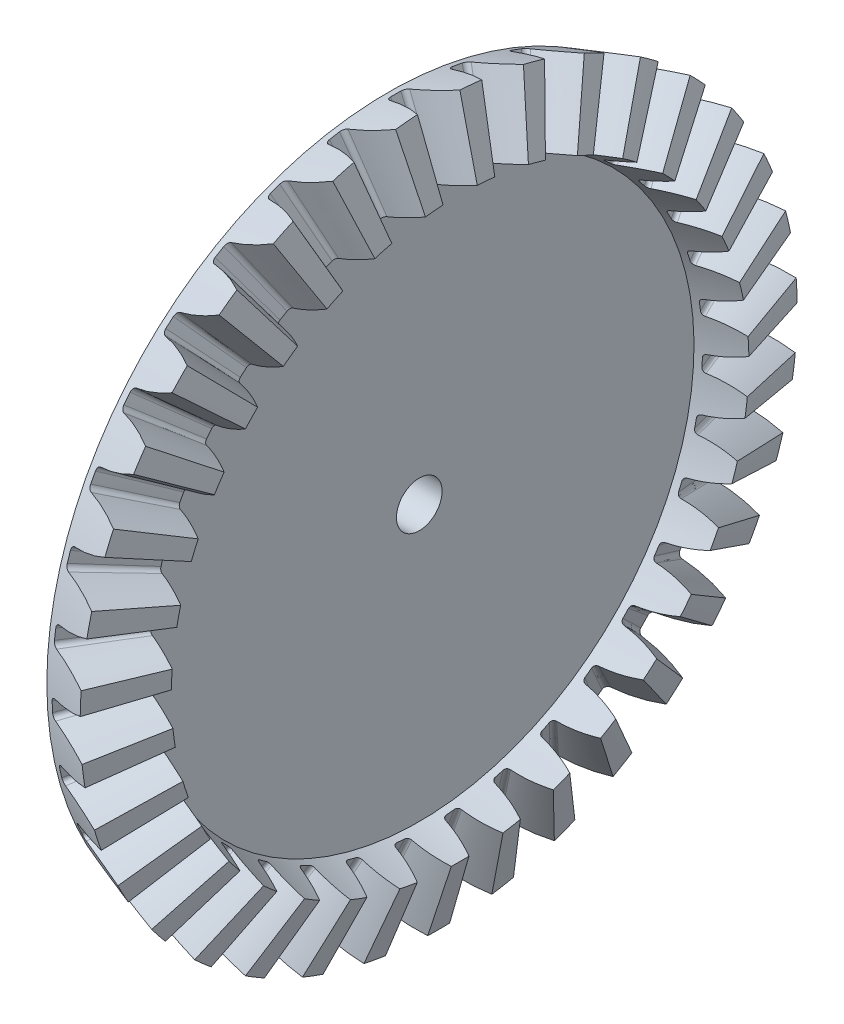
SolidWorks part; units mm, degrees
revolve "Base-Revolve" add sketch "BasProSke" angle 360 about L0 other way angle 5.143
sketch "BasProSke" plane through (0, 0, 0) normal (0, 1, 0) x (1, 0, 0)
  line L0 (-10, 0) -> (60, 0) construction
  line L1 (0, 0) -> (0, 17.8164)
  line L2 (0, 0) -> (1.6355, 0)
  line L3 (1.6355, 0) -> (1.6355, 14.3494)
  line L4 (8.4047, 0) -> (-8.2294, 48.5163) construction
  line L5 (0, 17.8164) -> (2.6495, 18.7247)
  line L6 (8.4047, 0) -> (-21.3703, 96.8732) construction
  line L7 (8.4047, 0) -> (0, 17.8164) construction
  line L8 (2.6495, 18.7247) -> (3.7694, 15.081)
  line L9 (3.7694, 15.081) -> (1.6355, 14.3494)
  line L10 (2.0547, 18.5208) -> (-9.9296, 18.5208) construction
  dimension "D1" = 35.6327
  dimension "D2" = 8.4047
  dimension "D3" = 19.5792
  dimension "D4" = 1.839
material "Plain Carbon Steel"
ref_plane "Plane1" through (0, 0, 0) normal (0, 0, 1) x (1, 0, 0)
ref_plane "Plane2" through (0, 0, 0) normal (0, 1, 0) x (1, 0, 0)
ref_plane "Plane3" through (0, 0, 0) normal (1, 0, 0) x (0, 0, -1)
sketch "HoldingSke" plane through (0, 0, 0) normal (0, 1, 0) x (1, 0, 0)
  line L0 (0, 0) -> (499.3551, -349.6522)
  line L1 (-15, 0) -> (100, 0) construction
  line L2 (0, 0) -> (-118.5727, 23.5047)
  line L3 (0, 0) -> (-11.863, 4.5341)
  line L4 (0, 0) -> (7.0742, 4.9534)
  line L5 (0, 0) -> (-11.8993, -4.4381)
  line L6 (0, 0) -> (-10.5278, -7.1032)
  line L7 (-118.5727, 23.5047) -> (-118.4773, 36.2044)
  line L8 (-76.2, 54.61) -> (-73.5584, 54.61)
  line L9 (-67.7845, 28.3722) -> (-49.3413, 33.142)
  line L10 (-76.2, 71.12) -> (104.1128, 71.12)
  line L11 (0, 0) -> (-3.81, 0)
  line L12 (-76.2, 101.6) -> (-76.1573, 101.6)
  line L13 (24.9733, 27.94) -> (52.9546, 28.2301)
  line L14 (24.9733, 27.94) -> (25.0241, 27.9398)
  line L15 (24.9733, 27.94) -> (100.3894, 30.0386)
  line L16 (-118.5727, 23.5047) -> (7.7133, -3.3382)
  circle A0 centre (0, 0) radius 1.1913
  circle A1 centre (0, 0) radius 6.35
  circle A2 centre (0, 0) radius 6.35
  circle A3 centre (0, 0) radius 1.1913
  dimension "Num_teeth" = 35
  dimension "Pitch_radius" = 180.3128
  dimension "Width" = 3.81
ref_plane "ToothPln" through (1.3247, 18.2706, 0) normal (-0.3243, 0.9459, 0) x (0, 0, -1)
ref_plane "ToothPln2" through (0.8841, -2.5785, 0) normal (-0.3243, 0.9459, 0) x (0, 0, 1)
sketch "TooCutSke" plane through (1.3247, 18.2706, 0) normal (-0.3243, 0.9459, 0) x (0, 0, -1)
  line L2 (0, 17.7491) -> (152.9193, -1681.3235) construction
  line L3 (0, 17.7491) -> (82.2353, -1767.4298) construction
  line L4 (0, -15.621) -> (0, 105.791) construction
  line L6 (-24.765, -1.4004) -> (21.082, -1.4004) construction
  line L7 (1.6602, -0.6971) -> (0.8515, -0.7344) construction
  arc A0 (-1.277, -1.7416) -> (1.277, -1.7416) centre (0, 17.7491) ccw
  arc A1 (-0.2632, 0.9681) -> (0.2632, 0.9681) centre (0, 17.7491) ccw
  circle A2 centre (0, 17.7491) radius 18.5208 construction
  circle A3 centre (0, 17.7491) radius 17.9309 construction
  arc A4 (0.515, 0.7483) -> (0.2632, 0.9681) centre (0.2671, 0.7183) ccw
  arc A5 (0.515, 0.7483) -> (1.277, -1.7416) centre (7.8698, 1.6375) ccw
  arc A6 (-1.277, -1.7416) -> (-0.515, 0.7483) centre (-7.8698, 1.6375) ccw
  arc A7 (-0.2632, 0.9681) -> (-0.515, 0.7483) centre (-0.2671, 0.7183) ccw
  ellipse E0 centre (0, 4.6725) end of major axis (18.7247, 4.6725) minor radius 6.0729 construction
sketch "TooCutSke2" plane through (0.8841, -2.5785, 0) normal (-0.3243, 0.9459, 0) x (0, 0, 1)
  line L0 (0, 0) -> (0, 68.072) construction
  line L2 (21.082, 5.7783) -> (-20.32, 5.7783) construction
  circle A0 centre (0, 7.9504) radius 0.0127
  ellipse E1 centre (0, 0) end of major axis (-17.8164, 0) minor radius 5.7783 construction
loft "ToothCut" cut profiles "TooCutSke2", "TooCutSke"
pattern_circular "TeethCuts" count 35 every 10.286 about axis through (-10, 0, 0) along (1, 0, 0) of "ToothCut"
sketch "HubSke" plane through (0, 0, 0) normal (-1, 0, 0) x (0, 0, 1)
  circle A0 centre (0, 0) radius 6.35
  dimension "Diameter" = 12.7
extrude "Hub" add sketch "HubSke" along normal blind 4.2954
sketch "BorSke" plane through (0, 0, 0) normal (1, 0, 0) x (0, 0, -1)
  circle A0 centre (0, 0) radius 1.1913
  dimension "Diameter" = 2.3825
extrude "Bore" cut sketch "BorSke" along normal mid plane 25.4001
sketch "KeySke" plane through (0, 0, 0) normal (1, 0, 0) x (0, 0, -1)
  line L0 (-0.127, 0) -> (-0.127, 1.4503)
  line L1 (-0.127, 1.4503) -> (0.127, 1.4503)
  line L2 (0.127, 1.4503) -> (0.127, 0)
  line L3 (0, 0) -> (0, 34) construction
  line L4 (-0.127, 0) -> (0.127, 0)
  dimension "Width" = 3.81
  dimension "Offset" = 1.4503
extrude "Keyway" [suppressed] cut sketch "KeySke" along normal mid plane 25.4001
pattern_circular "Keyway2" [suppressed] count 2 every 90 about axis through (-10, 0, 0) along (1, 0, 0) reverse direction yes
equation "' \"Pitch@HoldingSke\" = 4"
equation "' \"Num_teeth@HoldingSke\" = 20"
equation "' \"Mating_teeth@HoldingSke\" = 12"
equation "' \"Ap@HoldingSke\" =  20"
equation "' \"Ap@HoldingSke\" = 20"
equation "' \"Width@HoldingSke\" = 0.5"
equation "' \"Hub_dia@HoldingSke\"= 2"
equation "' \"Hub_dia@HoldingSke\" = 2"
equation "' \"Mounting_dist@HoldingSke\" = 3"
equation "' \"Bore@HoldingSke\" = 0.75"
equation "' \"T_dim@HoldingSke\" = 0.85"
equation "' \"Width@KeySke\" = 0.25"
equation "' \"Show_teeth@HoldingSke\" = 100"
equation "' \"Backlash@HoldingSke\" = 0.009"
equation "' \"Addendum_fac@HoldingSke\" = 1.0"
equation "' \"Dedendum_fac@HoldingSke\" = 1.188"
equation "' \"Dedendum_add@HoldingSke\" = 0.002"
equation "' \"Clearance_fac@HoldingSke\" = 0.188"
equation " \"Addendum_fac@HoldingSke\" = 0.54 + 0.46 / (\"Num_teeth@HoldingSke\" /  \"Mating_teeth@HoldingSke\" ) ^ 2"
equation "' \"Addendum_fac@HoldingSke\" = 2 - (0.54 + 0.46 / (\"Mating_teeth@HoldingSke\" /  \"Num_teeth@HoldingSke\" ) ^ 2)"
equation "\"Dedendum_fac@HoldingSke\" = 2.188 - \"Addendum_fac@HoldingSke\""
equation "\"Pitch_rad@BasProSke\" = \"Num_teeth@HoldingSke\" / \"Pitch@HoldingSke\" / 2"
equation "\"Pitch_ang@BasProSke\" = atn(\"Num_teeth@HoldingSke\" / \"Mating_teeth@HoldingSke\") * (180 / 3.14159265)"
equation "\"Addendum@BasProSke\" = \"Addendum_fac@HoldingSke\" / \"Pitch@HoldingSke\""
equation "\"Dedendum_plus@BasProSke\" = (\"Dedendum_fac@HoldingSke\" / \"Pitch@HoldingSke\" + \"Dedendum_add@HoldingSke\") * 1.25"
equation "\"Face_wid@BasProSke\" = \"Width@HoldingSke\""
equation "\"Radius@TooCutSke\" = ((\"Num_teeth@HoldingSke\" + 2 * \"Addendum_fac@HoldingSke\") / \"Pitch@HoldingSke\" ) / 2"
equation "\"Overcut_dia@TooCutSke\" =  1.02 * (\"Num_teeth@HoldingSke\" + 2 * \"Addendum_fac@HoldingSke\") / \"Pitch@HoldingSke\""
equation "\"Pitch_dia@TooCutSke\" = \"Num_teeth@HoldingSke\" / \"Pitch@HoldingSke\""
equation "\"Base_dia@TooCutSke\" = \"Num_teeth@HoldingSke\" / \"Pitch@HoldingSke\" * cos((\"Ap@HoldingSke\"  * 3.14159265 / 180))"
equation "'  \"Root_dia@TooCutSke\" =  (\"Num_teeth@HoldingSke\" + 2) / \"Pitch@HoldingSke\" - 2 * (\"Addendum_fac@HoldingSke\" + \"Dedendum_fac@HoldingSke\") / \"Pitch@HoldingSke\" - \"Dedendum_add@HoldingSke\" * 2"
equation "'  \"Root_dia@TooCutSke\" = (\"Num_teeth@HoldingSke\" + 2) / \"Pitch@HoldingSke\" - 2 * (\"Addendum_fac@HoldingSke\" + \"Dedendum_fac@HoldingSke\") / \"Pitch@HoldingSke\" - \"Dedendum_add@HoldingSke\" * 2"
equation "\"Root_dia@TooCutSke\" =  \"Num_teeth@HoldingSke\" / \"Pitch@HoldingSke\" - 2 * \"Dedendum_fac@HoldingSke\" / \"Pitch@HoldingSke\" - \"Dedendum_add@HoldingSke\" * 2"
equation "\"Half_ang@TooCutSke\" = 180 / \"Num_teeth@HoldingSke\""
equation "\"Half_CT@TooCutSke\" = \"Num_teeth@HoldingSke\" / \"Pitch@HoldingSke\" * sin((3.14159265 / 2 / \"Num_teeth@HoldingSke\")) / 2 - 2 * \"Backlash@HoldingSke\" / 4"
equation "\"Flank_rad@TooCutSke\" = \"Num_teeth@HoldingSke\" / \"Pitch@HoldingSke\" / 5"
equation "\"Root_fillet@TooCutSke\" = \"Clearance_fac@HoldingSke\" / \"Pitch@HoldingSke\" + \"Dedendum_add@HoldingSke\""
equation "\"Offset@ToothPln2\"  = \"Num_teeth@HoldingSke\" / \"Pitch@HoldingSke\" / 2 / sin(atn(\"Num_teeth@HoldingSke\" / \"Mating_teeth@HoldingSke\"))"
equation "\"Dedendum_plus@TooCutSke2\" = \"Dedendum_plus@BasProSke\""
equation "\"MHD@HoldingSke\" = \"Num_teeth@HoldingSke\" / \"Pitch@HoldingSke\" - 2 * \"Dedendum_plus@BasProSke\" * cos(atn(\"Num_teeth@HoldingSke\" / \"Mating_teeth@HoldingSke\"))"
equation "\"MBD@HoldingSke\" = \"Num_teeth@HoldingSke\" / \"Pitch@HoldingSke\" - 2 * \"Dedendum_plus@BasProSke\" * cos(atn(\"Num_teeth@HoldingSke\" / \"Mating_teeth@HoldingSke\")) - 0.002"
equation "\"MnMD@HoldingSke\" =  \"Num_teeth@HoldingSke\" / \"Pitch@HoldingSke\" / 2 / (\"Num_teeth@HoldingSke\" / \"Mating_teeth@HoldingSke\") + \"Dedendum_plus@BasProSke\" * sin(atn(\"Num_teeth@HoldingSke\" / \"Mating_teeth@HoldingSke\"))"
equation "\"OAL@HoldingSke\" = \"MnMD@HoldingSke\""
equation "\"MHD@HoldingSke\" = ((sgn( \"MHD@HoldingSke\" - \"Hub_dia@HoldingSke\" )-1)*( \"MHD@HoldingSke\" - \"Hub_dia@HoldingSke\" ))/-2+ \"Hub_dia@HoldingSke\""
equation "\"MBD@HoldingSke\" = ((sgn( \"MBD@HoldingSke\" - \"Bore@HoldingSke\" )-1)*( \"MBD@HoldingSke\" - \"Bore@HoldingSke\" ))/-2+ \"Bore@HoldingSke\""
equation "\"Face_wid@BasProSke\" = ((sgn( \"Face_wid@BasProSke\" - \"Offset@ToothPln2\" * 0.9)-1)*( \"Face_wid@BasProSke\" - \"Offset@ToothPln2\" * 0.9))/-2+ \"Offset@ToothPln2\" * 0.9"
equation "\"OAL@HoldingSke\" = ((sgn( \"OAL@HoldingSke\" - \"Mounting_dist@HoldingSke\" )+1)*( \"OAL@HoldingSke\" - \"Mounting_dist@HoldingSke\" ))/2 + \"Mounting_dist@HoldingSke\" + 0.000002"
equation "\"Num_teeth@TeethCuts\" = int( \"Show_teeth@HoldingSke\" ) + 1"
equation "\"Num_teeth@TeethCuts\" = ((sgn( \"Num_teeth@TeethCuts\" - \"Num_teeth@HoldingSke\" )-1)*( \"Num_teeth@TeethCuts\" - \"Num_teeth@HoldingSke\" ))/-2+ \"Num_teeth@HoldingSke\""
equation "\"Num_teeth@TeethCuts\" = ((sgn( \"Num_teeth@TeethCuts\" - 2.0)+1)*( \"Num_teeth@TeethCuts\" - 2.0))/2 +2.0"
equation "\"Angle@TeethCuts\" = 360.0 / \"Num_teeth@HoldingSke\""
equation "\"Diameter@HubSke\" = \"MHD@HoldingSke\""
equation "\"Length@Hub\" = \"OAL@HoldingSke\" - \"MnMD@HoldingSke\" + 0.000002"
equation "\"Diameter@BorSke\" = \"MBD@HoldingSke\""
equation "\"D1@Bore\" = \"OAL@HoldingSke\" * 2.0"
equation "\"D1@Keyway\" = \"OAL@HoldingSke\" * 2.0"
equation "\"Offset@KeySke\" = \"T_dim@HoldingSke\" - \"MBD@HoldingSke\" / 2.0"
